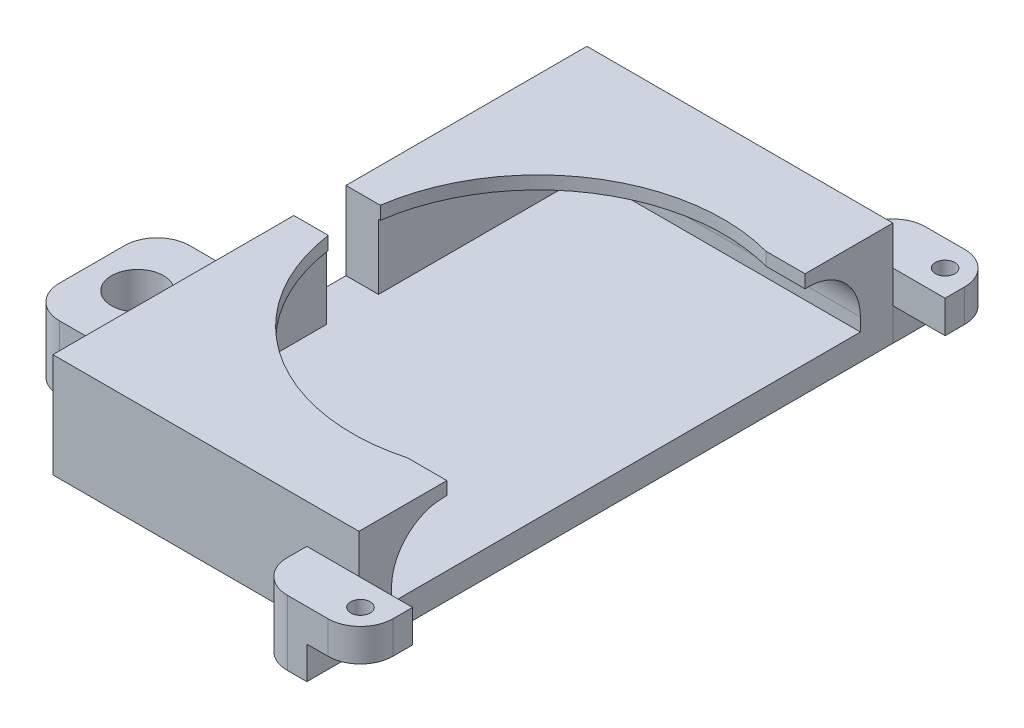
SolidWorks part; units mm, degrees
ref_plane "Front Plane" through (0, 0, 0) normal (0, 0, 1) x (1, 0, 0)
ref_plane "Top Plane" through (0, 0, 0) normal (0, 1, 0) x (1, 0, 0)
ref_plane "Right Plane" through (0, 0, 0) normal (1, 0, 0) x (0, 0, -1)
sketch "Sketch1" plane through (0, 0, 0) normal (0, 1, 0) x (1, 0, 0)
  line L0 (0, 41) -> (-47, 41)
  line L1 (-47, 41) -> (-47, -41)
  line L2 (-47, -41) -> (0, -41)
  ellipse E0 centre (0, 0) end of major axis (70, 0) minor radius 41 (0, -41) -> (0, 41) ccw
  dimension "D1" = 82
  dimension "D2" = 70
  dimension "D3" = 47
extrude "Boss-Extrude2" add sketch "Sketch1" along normal blind 14
sketch "Sketch3" plane through (0, 14, 0) normal (0, 1, 0) x (1, 0, 0)
  line L0 (0, 36) -> (-42, 36)
  line L1 (-42, 36) -> (-42, -36)
  line L2 (-42, -36) -> (0, -36)
  line L3 (-47, 41) -> (-47, -41) construction
  line L4 (0, 41) -> (-47, 41) construction
  ellipse E0 centre (0, 0) end of major axis (65, 0) minor radius 36 (0, -36) -> (0, 36) ccw
  dimension "D1" = 5
  dimension "D2" = 65
  dimension "D3" = 42
  dimension "D4" = 72
  dimension "D5" = 5
extrude "Cut-Extrude1" cut sketch "Sketch3" along normal through all from offset 10 offset against normal yes
sketch "Sketch5" plane through (0, 14, 0) normal (0, 1, 0) x (1, 0, 0)
  line L0 (8.5, 27.5) -> (-6.0167, 27.5)
  line L2 (-6.0167, -27.5) -> (8.5, -27.5)
  line L3 (-42, -36) -> (0, -36) construction
  line L4 (-42, 36) -> (-42, -36) construction
  line L5 (0, 41) -> (-47, 41) construction
  line L6 (-47, 41) -> (-47, -41)
  line L7 (-47, 41) -> (-47, -41) construction
  line L8 (0, 41) -> (-47, 41)
  line L9 (-47, 41) -> (-47, -41)
  line L10 (-47, -41) -> (0, -41)
  arc A0 (-20.7222, 27.5697) -> (-20.7222, -27.5697) centre (-13.5, 0) ccw
  arc A1 (-6.0167, 27.5) -> (-6.0167, -27.5) centre (-13.5, 0) ccw
  ellipse E0 centre (8.5, 0) end of major axis (-41.1528, 0) minor radius 27.5 (8.5, -27.5) -> (8.5, 27.5) ccw
  ellipse E1 centre (0, 0) end of major axis (70, 0) minor radius 41 (0, -41) -> (0, 41) ccw
  ellipse E2 centre (0, 0) end of major axis (70, 0) minor radius 41 (0, -41) -> (0, 41) ccw construction
  line M6 (-47, -41) -> (0, -41)
  ellipse M7 centre (0, 0) end of major axis (70, 0) minor radius 41 (0, -41) -> (0, 41) ccw
  line M8 (0, 41) -> (-47, 41)
  line M9 (-47, 41) -> (-47, -41)
  ellipse M10 centre (0, 0) end of major axis (65, 0) minor radius 36 (0, 36) -> (0, -36) cw
  line M11 (0, -36) -> (-42, -36)
  line M12 (-42, -36) -> (-42, 36)
  line M13 (-42, 36) -> (0, 36)
  dimension "D6" = 57
  dimension "D1" = 55
  dimension "D2" = 41.1528
  dimension "D3" = 49.6528
  dimension "D4" = 8.5
  dimension "D7" = 41
extrude "Boss-Extrude3" add sketch "Sketch5" along normal blind 2 contours E0 L2 A0 L0 M12 M11 M10 M13 | M9 M6 M7 M8 M13 M10 M11 M12
sketch "Sketch7" plane through (0, 16, 0) normal (0, 1, 0) x (1, 0, 0)
  line L0 (0, 41) -> (-0.005, 41)
  line L2 (0, -41) -> (0, 41)
  line L5 (0, 41) -> (-47, 41) construction
  line L6 (-0.005, 41) -> (-0.005, -41)
  line L7 (-47, -41) -> (0, -41) construction
  line L8 (-0.005, -41) -> (0, -41)
  dimension "D1" = 0.005
fillet "Fillet6" radius 8 3 edges at (65, 14, 0) (-21, 14, 36) (-21, 14, -36)
extrude "Cut-Extrude3" cut sketch "Sketch7" against normal through all
sketch "Sketch8" plane through (0, 0, 41) normal (0, 0, 1) x (1, 0, 0)
  line L0 (-47, 0) -> (-0.005, 0) construction
  line L1 (-8.005, 0) -> (-0.005, 0)
  line L2 (-8.005, 0) -> (-8.005, 10)
  line L3 (-8.005, 10) -> (0, 10)
  line L4 (-0.005, 0) -> (-0.005, 5)
  line L6 (-0.005, 0) -> (-0.005, 16) construction
  line L7 (0, 10) -> (8.2286, 10)
  line L9 (-0.005, 5) -> (8.2286, 5)
  line L10 (8.2286, 10) -> (8.2286, 5)
  dimension "D1" = 8
  dimension "D2" = 16.2336
  dimension "D3" = 5
  dimension "D4" = 10
extrude "Boss-Extrude4" add sketch "Sketch8" along normal blind 8
sketch "Sketch9" plane through (0, 10, 0) normal (0, 1, 0) x (1, 0, 0)
  line L0 (8.2286, -49) -> (8.2286, -41) construction
  line L1 (-8.005, -41) -> (-0.005, -41) construction
  circle A0 centre (4.2286, -45) radius 1.5
  dimension "D1" = 3
  dimension "D2" = 4
  dimension "D3" = 4
sketch "Sketch12" plane through (0, 0, 41) normal (0, 0, 1) x (1, 0, 0)
  line L0 (0, 0) -> (70, 0) construction
  line L1 (0, 4.95) -> (8.2286, 4.95)
  line L2 (0, 4.95) -> (0, 0)
  line L3 (0, 0) -> (8.2286, 0)
  line L4 (8.2286, 4.95) -> (8.2286, 0)
  line L5 (0, 16) -> (0, 0) construction
  line L6 (8.2286, 5) -> (8.2286, 10) construction
  line L8 (-0.005, 5) -> (8.2286, 5) construction
  dimension "D1" = 0.05
extrude "Boss-Extrude5" add sketch "Sketch12" along normal blind 10 from offset 2 offset against normal yes
extrude "Cut-Extrude4" cut sketch "Sketch9" against normal through all contours A0
sketch "Sketch13" plane through (0, 4, 0) normal (0, 1, 0) x (1, 0, 0)
  line L0 (-0.005, 0) -> (40.3204, 0) construction
  line L1 (68.4809, 8.4952) -> (77.8626, -17.4496)
  line L2 (-47, -41) -> (-0.005, -41) construction
  line L3 (72.5004, -27.3069) -> (25.7211, -38.1319)
  arc A0 (72.5004, -27.3069) -> (77.8626, -17.4496) centre (70.8095, -20) ccw
  ellipse E0 centre (0, 0) end of major axis (70, 0) minor radius 41 (0, -41) -> (0, 41) ccw construction
  ellipse E1 centre (0, 0) end of major axis (70, 0) minor radius 41 (25.7211, -38.1319) -> (68.4809, 8.4952) ccw
  dimension "D1" = 15
  dimension "D2" = 21
sketch "Sketch14" plane through (0, 0, -41) normal (0, 0, -1) x (-1, 0, 0)
  line L0 (0.005, 0) -> (47, 0) construction
  line L1 (8.005, 0) -> (0, 0)
  line L2 (8.005, 0) -> (8.005, 10)
  line L3 (8.005, 10) -> (-7.995, 10)
  line L4 (-7.995, 5) -> (-7.995, 10)
  line L5 (0.005, 0) -> (0.005, 16) construction
  line L7 (-7.995, 5) -> (0, 5)
  line L10 (0, 5) -> (0, 0)
  dimension "D1" = 10
  dimension "D2" = 8
  dimension "D3" = 5
  dimension "D4" = 16
extrude "Boss-Extrude6" add sketch "Sketch14" along normal blind 8
sketch "Sketch15" plane through (0, 0, -41) normal (0, 0, -1) x (-1, 0, 0)
  line L0 (8.005, 0) -> (47, 0) construction
  line L1 (-0.05, 0) -> (-7.995, 0)
  line L2 (-0.05, 0) -> (-0.05, 4.95)
  line L3 (-0.05, 4.95) -> (-7.995, 4.95)
  line L4 (-7.995, 0) -> (-7.995, 4.95)
  line L8 (-7.995, 10) -> (-7.995, 5) construction
  line L9 (-7.995, 5) -> (0, 5) construction
  line L10 (0, 5) -> (0, 0) construction
  dimension "D1" = 0.05
  dimension "D2" = 0.05
extrude "Boss-Extrude15" add sketch "Sketch15" along normal blind 10 from offset 2 offset against normal yes
sketch "Sketch16" plane through (0, 10, 0) normal (0, 1, 0) x (1, 0, 0)
  line L0 (-0.005, 41) -> (7.995, 41) construction
  line L1 (7.995, 49) -> (7.995, 41) construction
  circle A0 centre (3.995, 45) radius 1.5
  dimension "D1" = 3
  dimension "D2" = 4
  dimension "D3" = 4
extrude "Cut-Extrude5" cut sketch "Sketch16" against normal through all
fillet "Fillet9" radius 5 1 edges at (7.995, 7.5, -49)
fillet "Fillet10" radius 5 1 edges at (7.995, 2.475, -49)
fillet "Fillet11" radius 5 1 edges at (-8.005, 5, -49)
fillet "Fillet12" radius 5 2 edges at (8.2286, 7.5, 49) (-8.005, 5, 49)
fillet "Fillet13" radius 5 1 edges at (8.2286, 2.475, 49)
extrude "Boss-Extrude16" add sketch "Sketch13" along normal blind 10 from offset 4 offset against normal yes
sketch "Sketch18" plane through (0, 10, 0) normal (0, 1, 0) x (1, 0, 0)
  circle A0 centre (70.8095, -20) radius 4
  arc A1 (72.5004, -27.3069) -> (77.8626, -17.4496) centre (70.8095, -20) ccw construction
  dimension "D1" = 8
extrude "Cut-Extrude6" cut sketch "Sketch18" against normal through all contours A0
sketch "Sketch19" plane through (-47, 0, 0) normal (-1, 0, 0) x (0, 0, 1)
  line L0 (-41, 0) -> (41, 0) construction
  line L1 (10, 0) -> (30, 0)
  line L2 (10, 0) -> (10, 10)
  line L3 (10, 10) -> (30, 10)
  line L4 (30, 0) -> (30, 10)
  line L6 (-41, 16) -> (-41, 0) construction
  dimension "D1" = 10
  dimension "D2" = 20
  dimension "D3" = 51
extrude "Boss-Extrude17" add sketch "Sketch19" along normal blind 15
sketch "Sketch20" plane through (0, 10, 0) normal (0, 1, 0) x (1, 0, 0)
  line L0 (-62, -30) -> (-47, -30) construction
  line L1 (-47, -30) -> (-47, -10) construction
  circle A0 centre (-55, -20) radius 4
  dimension "D1" = 8
  dimension "D2" = 10
  dimension "D3" = 8
extrude "Cut-Extrude7" cut sketch "Sketch20" against normal through all
fillet "Fillet14" radius 5 2 edges at (-62, 5, 10) (-62, 5, 30)
sketch "Sketch21" plane through (-47, 0, 0) normal (-1, 0, 0) x (0, 0, 1)
  line L0 (-4, 16) -> (-4, 4)
  line L1 (-41, 16) -> (41, 16) construction
  line L2 (-4, 4) -> (4, 4)
  line L3 (4, 4) -> (4, 16)
  line L5 (-41, 0) -> (10, 0) construction
  line L6 (-4, 16) -> (4, 16)
  line L7 (-41, 16) -> (-41, 0) construction
  dimension "D1" = 8
  dimension "D2" = 37
  dimension "D4" = 4
extrude "Cut-Extrude9" cut sketch "Sketch21" against normal up to next
sketch "Croquis1" plane through (0, 0, 0) normal (0, -1, 0) x (-1, 0, 0)
  line L1 (0, -49) -> (-114.882, -49)
  line L2 (0, -49) -> (0, 112.642)
  line L3 (0, 112.642) -> (-114.882, 112.642)
  line L4 (-114.882, -49) -> (-114.882, 112.642)
extrude "Cortar-Extruir2" cut sketch "Croquis1" against normal blind 4.95
sketch "Croquis2" plane through (0, 4.95, 0) normal (0, -1, 0) x (-1, 0, 0)
  line L1 (0, -41) -> (-88.2055, -41)
  line L2 (0, -41) -> (0, 41)
  line L3 (0, 41) -> (-88.2055, 41)
  line L4 (-88.2055, -41) -> (-88.2055, 41)
extrude "Cortar-Extruir3" cut sketch "Croquis2" against normal blind 51.95
